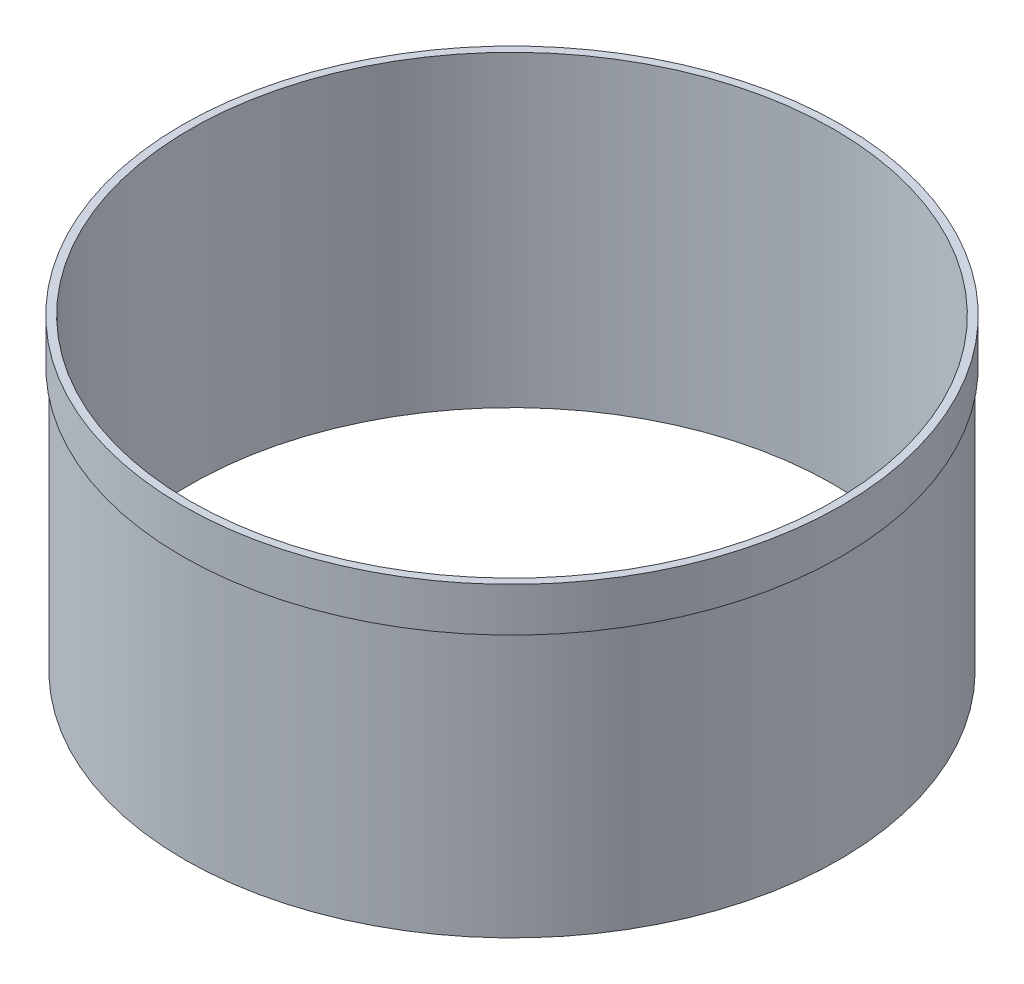
SolidWorks part; units mm, degrees
material "A-Glass Fiber"
ref_plane "Front Plane" through (0, 0, 0) normal (0, 0, 1) x (1, 0, 0)
ref_plane "Top Plane" through (0, 0, 0) normal (0, 1, 0) x (1, 0, 0)
ref_plane "Right Plane" through (0, 0, 0) normal (1, 0, 0) x (0, 0, -1)
sketch "Sketch1" plane through (0, 0, 0) normal (0, 1, 0) x (1, 0, 0)
  circle A0 centre (0, 0) radius 94.615
  circle A1 centre (0, 0) radius 93.0275
  dimension "D1" = 1.5875
  dimension "D2" = 189.23
extrude "Boss-Extrude1" add sketch "Sketch1" along normal blind 88.9
sketch "Sketch2" plane through (0, 88.9, 0) normal (0, 1, 0) x (1, 0, 0)
  circle A0 centre (0, 0) radius 94.615 construction
  circle A1 centre (0, 0) radius 94.615
  circle A2 centre (0, 0) radius 95.25
  dimension "D1" = 190.5
extrude "Boss-Extrude2" add sketch "Sketch2" against normal blind 12.7
